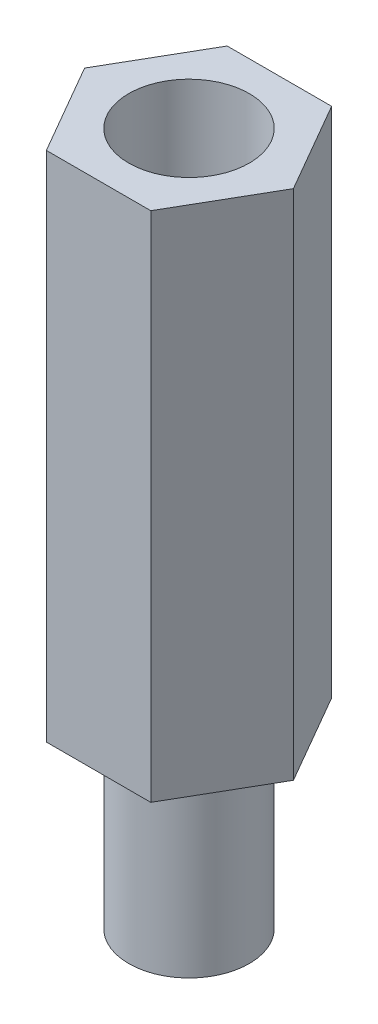
SolidWorks part; units mm, degrees
material "铜"
ref_plane "前视基准面" through (0, 0, 0) normal (0, 0, 1) x (1, 0, 0)
ref_plane "上视基准面" through (0, 0, 0) normal (0, 1, 0) x (1, 0, 0)
ref_plane "右视基准面" through (0, 0, 0) normal (1, 0, 0) x (0, 0, -1)
sketch "草图2" plane through (0, 0, 0) normal (0, 1, 0) x (1, 0, 0)
  line L1 (3.4641, 0) -> (1.7321, 3)
  line L2 (1.7321, 3) -> (-1.7321, 3)
  line L3 (-1.7321, 3) -> (-3.4641, 0)
  line L4 (-3.4641, 0) -> (-1.7321, -3)
  line L5 (-1.7321, -3) -> (1.7321, -3)
  line L6 (1.7321, -3) -> (3.4641, 0)
  circle A0 centre (0, 0) radius 3 construction
  circle A1 centre (0, 0) radius 2
  dimension "D2" = 4
  dimension "D1" = 6
extrude "凸台-拉伸1" add sketch "草图2" along normal blind 17
extrude "凸台-拉伸2" add sketch "草图2<2>" against normal blind 6 separate body contours A1 region at (0, 0, 0)
sketch "草图2<2>" plane through (0, 0, 0) normal (0, 1, 0) x (1, 0, 0) same geometry as "草图2"
